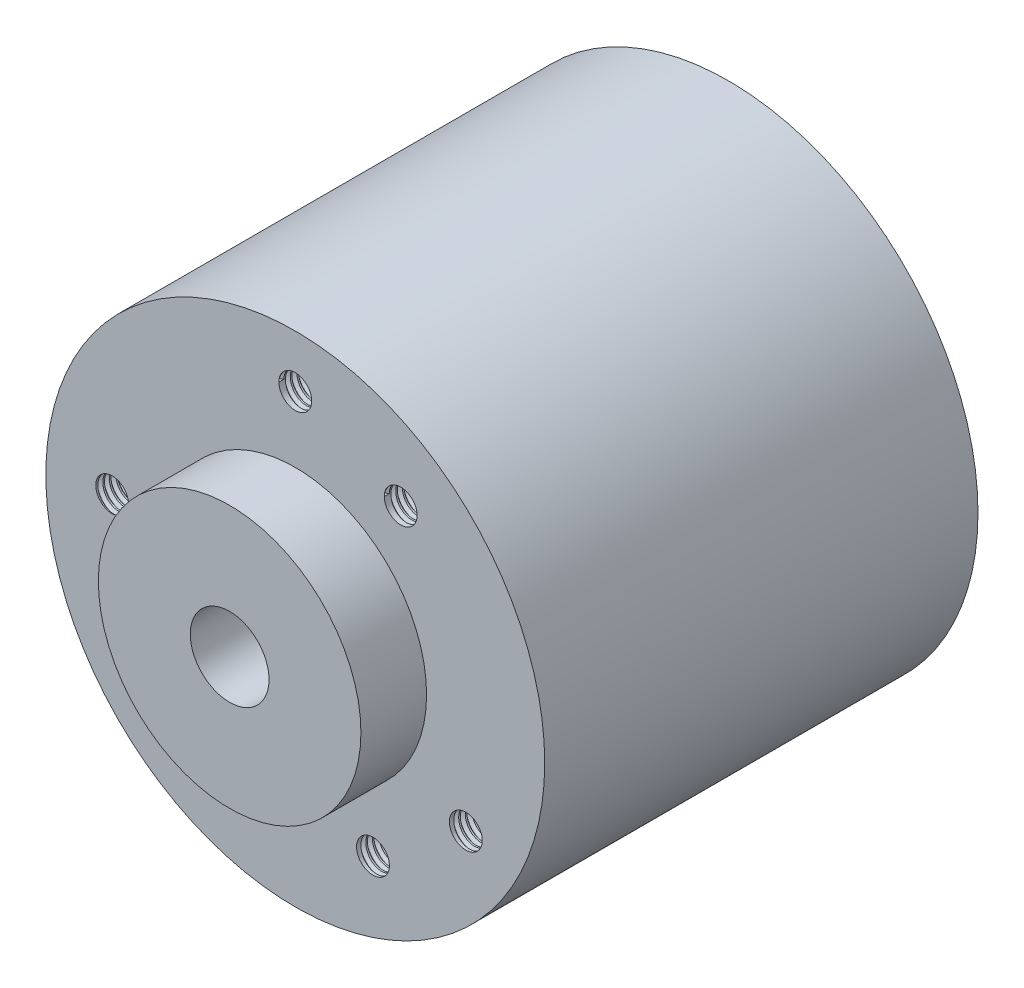
SolidWorks part; units mm, degrees
ref_plane "Frontal Plane" through (0, 0, 0) normal (0, 0, 1) x (1, 0, 0)
ref_plane "Horizontal Plane" through (0, 0, 0) normal (0, 1, 0) x (1, 0, 0)
ref_plane "Profile Plane" through (0, 0, 0) normal (1, 0, 0) x (0, 0, -1)
sketch "Sketch1" plane through (0, 0, 0) normal (1, 0, 0) x (0, 0, -1)
  line L0 (0, 0) -> (0, 19)
  line L1 (0, 19) -> (-33, 19)
  line L2 (-33, 19) -> (-33, 10)
  line L3 (-33, 10) -> (-38, 10)
  line L4 (-38, 10) -> (-38, 3)
  line L5 (-38, 3) -> (-33, 3)
  line L6 (-33, 3) -> (-33, 0)
  line L7 (-33, 0) -> (0, 0)
  line L8 (0, 0) -> (30.5675, 0) construction
  dimension "D1" = 19
  dimension "D2" = 33
  dimension "D3" = 3
  dimension "D4" = 5
  dimension "D5" = 10
revolve "Revolve1" add sketch "Sketch1" angle 360 about L8
sketch "Sketch2" plane through (0, 0, 33) normal (0, 0, 1) x (1, 0, 0)
  circle A0 centre (0, 0) radius 15 construction
  point P4 (0, 15)
  dimension "D1" = 30
hole_wizard "Ø2.5 (2.5) Diameter Hole1" positions "Sketch2" profile "Sketch3" hole size "Ø2.5" standard "ANSI Metric"
sketch "Sketch3" plane through (0, 15, 33) normal (1, 0, 0) x (0, -1, 0)
  line L0 (0, 0) -> (0, 8.2511)
  line L1 (0, 8.2511) -> (1.25, 7.5)
  line L2 (1.25, 7.5) -> (1.25, 0)
  line L5 (1.25, 0) -> (0, 0)
  line L10 (0, 8.2511) -> (-1.25, 7.5) construction
  line L11 (0, -6.35) -> (0, 107.95) construction
  dimension "Hole Dia." = 2.5
  dimension "Hole Depth" = 7.5
  dimension "Drill Angle" = 118
thread "Thread1" pitch 0.5 method cut profile "Thread Profile1" start angle 0, offset 0, length 6, pitch 0.5, diameter 2.5
ref_plane "Plane1" through (-1.25, 15, 33) normal (0, -1, 0) x (-1, 0, 0)
sketch "Thread Profile1" plane through (-1.25, 15, 33) normal (0, -1, 0) x (-1, 0, 0)
  line L0 (0, 0) -> (0, 0.5) construction
  line L1 (0, 0) -> (0.2706, 0.1562)
  line L2 (0.2706, 0.1562) -> (0.2706, 0.2187)
  line L3 (0.2706, 0.2187) -> (0, 0.375)
  line L4 (0.2706, 0.1875) -> (0, 0.1875) construction
  line L11 (0, 0) -> (0, 0.375)
  point P2 (0, 0)
  dimension "Pitch" = 0.5
  dimension "Profile_Angle" = 60
  dimension "Profile_Land" = 0.0625
  dimension "Profile_Height" = 0.2706
sketch "Sketch7" plane through (0, 0, 33) normal (0, 0, 1) x (1, 0, 0)
  line L0 (0, 14) -> (0, 0) construction
  line L1 (0, 0) -> (8.0301, 11.4681) construction
  circle A0 centre (0, 0) radius 14 construction
  point P4 (8.0301, 11.4681)
  point P9 (8.0301, 11.4681)
  dimension "D1" = 28
  dimension "D2" = 35
hole_wizard "Ø2.5 (2.5) Diameter Hole2" positions "Sketch7" profile "Sketch8" hole size "Ø2.5" standard "ANSI Metric"
sketch "Sketch8" plane through (8.0301, 11.4681, 33) normal (1, 0, 0) x (0, -1, 0)
  line L0 (0, 0) -> (0, 8.2511)
  line L1 (0, 8.2511) -> (1.25, 7.5)
  line L2 (1.25, 7.5) -> (1.25, 0)
  line L5 (1.25, 0) -> (0, 0)
  line L10 (0, 8.2511) -> (-1.25, 7.5) construction
  line L11 (0, -6.35) -> (0, 107.95) construction
  dimension "Hole Dia." = 2.5
  dimension "Hole Depth" = 7.5
  dimension "Drill Angle" = 118
thread "Thread2" pitch 0.5 method cut profile "Thread Profile2" start angle 0, offset 0, length 6, pitch 0.5, diameter 2.5
ref_plane "Plane2" through (6.7801, 11.4681, 33) normal (0, -1, 0) x (-1, 0, 0)
sketch "Thread Profile2" plane through (6.7801, 11.4681, 33) normal (0, -1, 0) x (-1, 0, 0)
  line L0 (0, 0) -> (0, 0.5) construction
  line L1 (0, 0) -> (0.2706, 0.1562)
  line L2 (0.2706, 0.1562) -> (0.2706, 0.2187)
  line L3 (0.2706, 0.2187) -> (0, 0.375)
  line L4 (0.2706, 0.1875) -> (0, 0.1875) construction
  line L11 (0, 0) -> (0, 0.375)
  point P2 (0, 0)
  dimension "Pitch" = 0.5
  dimension "Profile_Angle" = 60
  dimension "Profile_Land" = 0.0625
  dimension "Profile_Height" = 0.2706
pattern_circular "CirPattern1" count 3 over 360 about axis through (0, 0, 33) along (0, 0, 1) of "Thread1", "Ø2.5 (2.5) Diameter Hole1", "Thread2", "Ø2.5 (2.5) Diameter Hole2"
equation "\"BaseL\"= 6ft"
equation "\"BaseW\"= 5.5in"
equation "\"BaseThickness\"= 1in"
equation "\"RailGap\"= 4cm"
equation "\"SlidePlateL\"= 8cm"
equation "\"SlidePlateW\"= 11cm"
equation "\"SlidePlateThickness\"= 5mm"
equation "\"SlidePlateClearance\"= 1cm"
equation "\"BoxThickness\"= .5cm"
equation "\"BoxX\"= \"RailGap\" + 30mm"
equation "\"BoxH\"= 2cm + \"SlidePlateClearance\" + \"SlidePlateThickness\" + 3cm"
equation "\"PulleyRadius\"= 15.1mm"
equation "\"PulleyH\"= 30mm + 21.4056mm - 2.5mm"
equation "\"PulleyShaftDiameter\"= .3125in"
equation "\"PulleyShaftL\"= 4in"
equation "\"PulleyShaft2L\"= 3in"
equation "\"MotorL\"= 4.43in"
equation "\"MotorRadius\"= 1.291in"
equation "\"MotorShaftRadius\"= .15625in"
equation "\"MotorShaftL\"= 1.75in"
equation "\"HeadstoneThickness\"= 7.5mm"
equation "\"BeltL\"= 1500mm + \"80\""
equation "\"BeltThickness\"= 2.5mm"
equation "\"BeltW\"= .375in"
equation "\"BeltLockH\"= \"PulleyH\" + 19.4056mm - (\"SlidePlateThickness\" + \"SlidePlateClearance\" + 15mm + 5mm)"
equation "\"EncoderL\"= 33mm"
equation "\"EncoderRadius\"= 19mm"
equation "\"EncoderShaftRadius\"= 3mm"
equation "\"EncoderShaftL\"= 15mm"
equation "\"D1@Sketch1\"=\"EncoderRadius\""
equation "\"D2@Sketch1\"=\"EncoderL\""
equation "\"D3@Sketch1\"=\"EncoderShaftRadius\""
